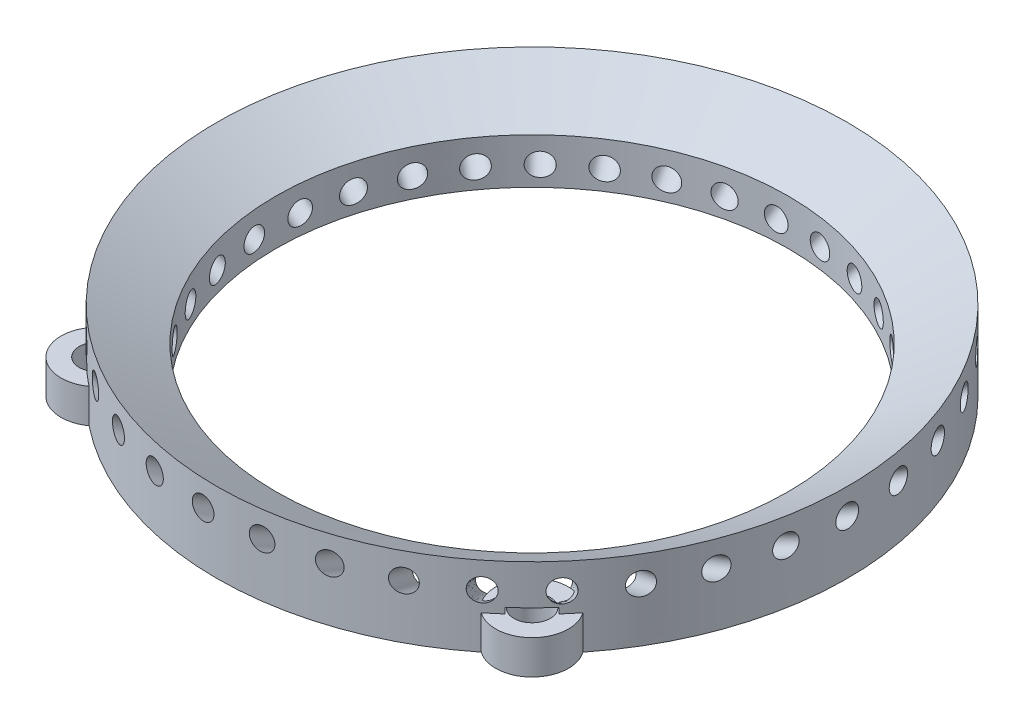
SolidWorks part; units mm, degrees
material "ABS"
ref_plane "Alzado" through (0, 0, 0) normal (0, 0, 1) x (1, 0, 0)
ref_plane "Planta" through (0, 0, 0) normal (0, 1, 0) x (1, 0, 0)
ref_plane "Vista lateral" through (0, 0, 0) normal (1, 0, 0) x (0, 0, -1)
sketch "Croquis2" plane through (0, 0, 0) normal (0, 0, 1) x (1, 0, 0)
  line L0 (0, 0) -> (-22.5, 0) construction
  line L1 (-22.5, 0) -> (-22.5, 1)
  line L2 (-22.5, 1) -> (-22.5, 4)
  line L3 (-22.5, 0) -> (-27.7, 0)
  line L4 (-27.7, 0) -> (-27.7, 7.0022)
  line L5 (-27.7, 7.0022) -> (-22.5, 4)
  line L6 (0, 0) -> (0, 4.6512) construction
  dimension "D1" = 22.5
  dimension "D2" = 1
  dimension "D3" = 3
  dimension "D4" = 27.7
  dimension "D5" = 30
revolve "Revolución1" add sketch "Croquis2" angle 360 about L6
ref_plane "Plano1" through (27.7, 0, 0) normal (1, 0, 0) x (0, 0, -1)
sketch "Croquis3" plane through (27.7, 0, 0) normal (1, 0, 0) x (0, 0, -1)
  circle A0 centre (0, 4.75) radius 1
  point P4 (0, 0)
  dimension "D1" = 4.75
  dimension "D2" = 2
ref_plane "Plano2" through (0, 0, 0) normal (0, 0, -1) x (-1, 0, 0)
sketch "Croquis4" plane through (0, 0, 0) normal (0, 0, -1) x (-1, 0, 0)
  line L0 (-27.7, 4.75) -> (-19.4728, 0) construction
  line L1 (-19.4728, 0) -> (-27.7, 0) construction
  dimension "D1" = 30
extrude "Cortar-Extruir1" cut sketch "Croquis3" along direction (-0.866, -0.5, 0) on the side against the normal up to vertex (8.2272 mm away) up to point (19.4728, 0, 0)
pattern_circular "MatrizC1" count 35 over 360 about axis through (0, 0, 0) along (0, -1, 0) of "Cortar-Extruir1"
sketch "Croquis5" plane through (0, 0, 0) normal (0, -1, 0) x (1, 0, 0)
  line L0 (0, 0) -> (-19.0919, 19.0919) construction
  line L2 (0, 0) -> (0, -25.1) construction
  line L3 (0, 0) -> (-23.5863, -8.5847) construction
  circle A2 centre (0, -25.1) radius 1.8
  circle A6 centre (0, 0) radius 25.1 construction
  circle A9 centre (-23.5863, -8.5847) radius 1.8
  circle A10 centre (-19.0919, 19.0919) radius 1.8
  circle A11 centre (19.0919, 19.0919) radius 1.8
  circle A12 centre (23.5863, -8.5847) radius 1.8
  point P18 (0, 0)
  dimension "D1" = 3.6
  dimension "D2" = 50.2
  dimension "D4" = 3.6
  dimension "D7" = 3.6
  dimension "D3" = 70
  dimension "D5" = 27
  dimension "D6" = 135
extrude "Cortar-Extruir2" cut sketch "Croquis5" against normal blind 3.5
sketch "Croquis6" plane through (0, 0, 0) normal (0, -1, 0) x (1, 0, 0)
  line L0 (0, 0) -> (0, -22.5) construction
  line L1 (-19.0919, 20.6919) -> (-19.0919, 22.2919) construction
  circle A0 centre (-19.0919, 19.0919) radius 1.6
  circle A2 centre (0, 0) radius 22.5 construction
  circle A3 centre (19.0919, 19.0919) radius 1.6
  circle A5 centre (0, 0) radius 30.2 construction
  circle A6 centre (-19.0919, 19.0919) radius 3.2
  circle A7 centre (19.0919, 19.0919) radius 3.2
  dimension "D1" = 1.6
  dimension "D2" = 3.2
extrude "Saliente-Extruir1" add sketch "Croquis6" against normal blind 3
